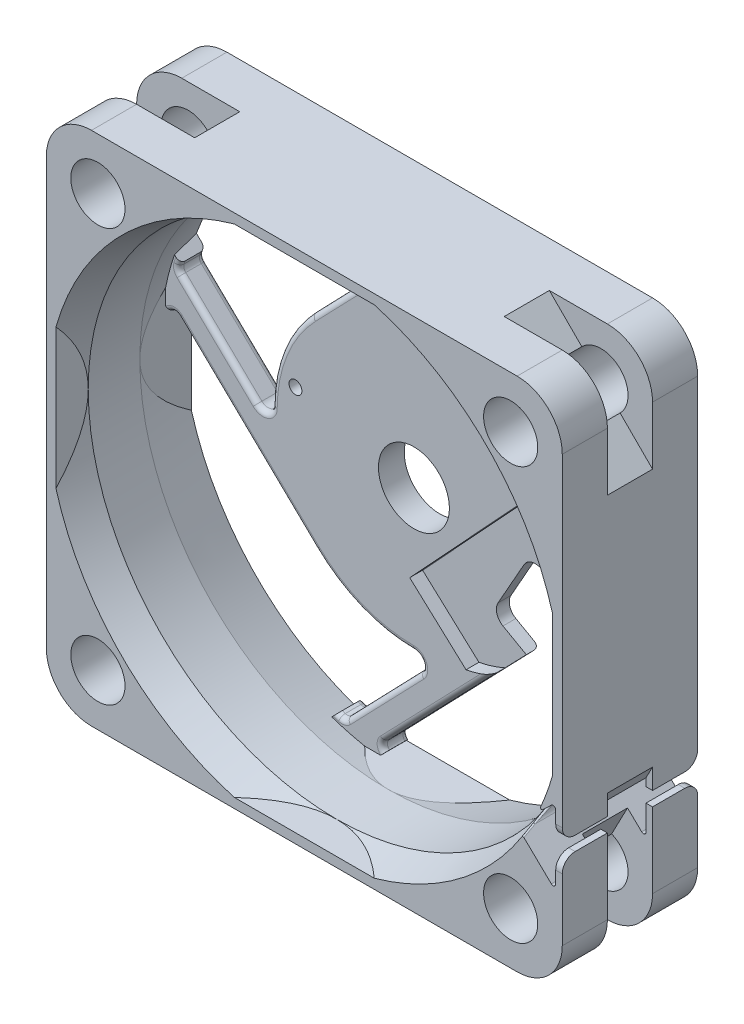
SolidWorks part; units mm, degrees
material "ПК/АБС"
ref_plane "Front" through (0, 0, 0) normal (0, 0, 1) x (1, 0, 0)
ref_plane "Top" through (0, 0, 0) normal (0, 1, 0) x (1, 0, 0)
ref_plane "Right" through (0, 0, 0) normal (1, 0, 0) x (0, 0, -1)
sketch "Эскиз1" plane through (0, 0, 0) normal (0, 0, 1) x (1, 0, 0)
  line L1 (-16.5, 20) -> (16.5, 20)
  line L2 (-20, 16.5) -> (-20, -16.5)
  line L3 (-16.5, -20) -> (16.5, -20)
  line L4 (20, 16.5) -> (20, -16.5)
  line L5 (0, -20) -> (0, 20) construction
  line L6 (-20, 0) -> (20, 0) construction
  arc A0 (16.5, 20) -> (20, 16.5) centre (16.5, 16.5) cw
  arc A1 (-20, -16.5) -> (-16.5, -20) centre (-16.5, -16.5) ccw
  arc A2 (-16.5, 20) -> (-20, 16.5) centre (-16.5, 16.5) ccw
  arc A3 (16.5, -20) -> (20, -16.5) centre (16.5, -16.5) ccw
  point P0 (0, 0)
  point P11 (-20, -20)
  point P14 (-20, 20)
  dimension "D2" = 3.5
  dimension "D1" = 40
extrude "Бобышка-Вытянуть1" add sketch "Эскиз1" along normal blind 10.5
sketch "Эскиз2" plane through (0, 0, 10.5) normal (0, 0, 1) x (1, 0, 0)
  circle A0 centre (0, 0) radius 19.25
  dimension "D1" = 38.5
extrude "Вырез-Вытянуть1" cut sketch "Эскиз2" against normal blind 10.5
sketch "Эскиз3" plane through (0, 0, 0) normal (0, 1, 0) x (1, 0, 0)
  line L0 (0, 0) -> (0, -4) construction
  line L1 (-16.5, 0) -> (16.5, 0) construction
  line L2 (0, -10.5) -> (0, -8) construction
  line L3 (-16.5, -10.5) -> (16.5, -10.5) construction
  line L4 (0, -10.5) -> (-20, -10.5)
  line L5 (-20, -10.5) -> (-19.25, -8)
  line L6 (-19.25, -8) -> (0, -8)
  line L7 (0, 0) -> (-20, 0)
  line L8 (-20, 0) -> (-19.25, -4)
  line L9 (-19.25, -4) -> (0, -4)
  line L10 (0, -10.5) -> (0, -8)
  line L11 (0, -4) -> (0, 0)
  dimension "D1" = 19.25
  dimension "D2" = 20
  dimension "D3" = 4
  dimension "D4" = 2.5
revolve "Вырез-Повернуть1" cut sketch "Эскиз3" angle 360 about L10
sketch "Эскиз4" plane through (0, 0, 10.5) normal (0, 0, 1) x (1, 0, 0)
  line L1 (16.5, -20) -> (-16.5, -20)
  line L2 (20, -16.5) -> (20, 16.5)
  line L3 (16.5, 20) -> (-16.5, 20)
  line L4 (-20, -16.5) -> (-20, 16.5)
  line L5 (0, 20) -> (0, -20) construction
  line L6 (20, 0) -> (-20, 0) construction
  line L7 (-15.75, 19.25) -> (15.75, 19.25)
  line L8 (-19.25, 15.75) -> (-19.25, -15.75)
  line L9 (-15.75, -19.25) -> (15.75, -19.25)
  line L10 (19.25, 15.75) -> (19.25, -15.75)
  line L11 (0, -19.25) -> (0, 19.25) construction
  line L12 (-19.25, 0) -> (19.25, 0) construction
  arc A0 (-16.5, -20) -> (-20, -16.5) centre (-16.5, -16.5) cw
  arc A1 (-19.25, -15.75) -> (-15.75, -19.25) centre (-15.75, -15.75) ccw
  arc A2 (15.75, -19.25) -> (19.25, -15.75) centre (15.75, -15.75) ccw
  arc A3 (16.5, -20) -> (20, -16.5) centre (16.5, -16.5) ccw
  arc A4 (15.75, 19.25) -> (19.25, 15.75) centre (15.75, 15.75) cw
  arc A5 (20, 16.5) -> (16.5, 20) centre (16.5, 16.5) ccw
  arc A6 (-16.5, 20) -> (-20, 16.5) centre (-16.5, 16.5) ccw
  arc A7 (-15.75, 19.25) -> (-19.25, 15.75) centre (-15.75, 15.75) ccw
  point P0 (0, 0)
  point P4 (0, 0)
  point P18 (-19.25, -19.25)
  point P23 (20, -20)
  point P28 (20, 20)
  point P33 (-19.25, 19.25)
  dimension "D3" = 3.5
  dimension "D1" = 40
  dimension "D2" = 38.5
extrude "Бобышка-Вытянуть2" add sketch "Эскиз4" against normal blind 10.5
sketch "Эскиз5" plane through (0, 0, 10.5) normal (0, 0, 1) x (1, 0, 0)
  line L1 (-16, 16) -> (16, 16) construction
  line L2 (-16, 16) -> (-16, -16) construction
  line L3 (-16, -16) -> (16, -16) construction
  line L4 (16, 16) -> (16, -16) construction
  line L5 (0, -16) -> (0, 16) construction
  line L6 (-16, 0) -> (16, 0) construction
  circle A0 centre (-16, 16) radius 2.1
  circle A1 centre (16, 16) radius 2.1
  circle A2 centre (16, -16) radius 2.1
  circle A3 centre (-16, -16) radius 2.1
  point P0 (0, 0)
  point P17 (0, 0)
  dimension "D2" = 4.2
  dimension "D1" = 32
  dimension "D3" = 4
extrude "Вырез-Вытянуть2" cut sketch "Эскиз5" against normal blind 10.5
sketch "Эскиз6" plane through (0, 0, 10.5) normal (0, 0, 1) x (1, 0, 0)
  line L0 (-12, 20) -> (-20, 12)
  line L1 (16.5, 20) -> (-16.5, 20) construction
  line L2 (-20, 16.5) -> (-20, -16.5) construction
  line L3 (0, 20) -> (0, -20) construction
  line L4 (-16.5, -20) -> (16.5, -20) construction
  line L5 (0, -20) -> (-20, 0) construction
  line L6 (-20, 0) -> (20, 0) construction
  line L7 (20, -16.5) -> (20, 16.5) construction
  line L8 (-12, 20) -> (-20, 20)
  line L9 (-20, 20) -> (-20, 12)
  line L10 (20, 20) -> (12, 20)
  line L11 (20, 12) -> (12, 20)
  line L12 (20, 12) -> (20, 20)
  line L13 (20, -20) -> (20, -12) construction
  line L14 (12, -20) -> (20, -12) construction
  line L15 (12, -20) -> (20, -20) construction
  line L16 (-20, -20) -> (-12, -20)
  line L17 (-20, -12) -> (-12, -20)
  line L18 (-20, -12) -> (-20, -20)
  line L19 (12, -20) -> (20, -8) construction
  line L20 (20, -8) -> (20, -20)
  line L21 (20, -20) -> (12, -20)
  line L22 (12, -20) -> (15.6268, -16.3732)
  line L23 (15.6268, -16.3732) -> (20, -8)
  point P27 (0, 0)
  dimension "D1" = 12
  dimension "D2" = 12
  dimension "D3" = 4
  dimension "D4" = 12
extrude "Вырез-Вытянуть3" cut sketch "Эскиз6" against normal blind 3.5 from offset 3.5 offset against normal yes
sketch "Эскиз7" plane through (0, 0, 0) normal (0, 0, -1) x (-1, 0, 0)
  line L0 (7.9198, 7.634) -> (-4, 20) construction
  line L1 (-20, 20) -> (20, 20) construction
  line L2 (-20, 20) -> (-20, -20) construction
  line L3 (-20, -20) -> (20, -20) construction
  line L4 (20, 20) -> (20, -20) construction
  line L5 (0, -20) -> (0, 20) construction
  line L6 (-20, 0) -> (20, 0) construction
  line L7 (-7.0556, 20) -> (1.7554, 10.859) construction
  line L8 (-3.3055, 20) -> (-2.299, 18.9558)
  line L9 (-7.7501, 20) -> (-5.9584, 18.1412)
  line L10 (-3.3055, 20) -> (-7.7501, 20)
  line L11 (-5.9584, 18.1412) -> (-6.6524, 18.8612) construction
  line L12 (-5.4246, 18.3079) -> (0.4766, 12.1858)
  line L13 (7.9198, 7.634) -> (-2.9121, 18.8713)
  line L14 (-2.299, 18.9558) -> (-2.9121, 18.8713)
  line L15 (-5.4246, 18.3079) -> (-5.9584, 18.1412)
  line L16 (20, 3.3055) -> (18.9558, 2.299)
  line L17 (20, 7.7501) -> (18.1412, 5.9584)
  line L18 (20, 3.3055) -> (20, 7.7501)
  line L19 (18.3079, 5.4246) -> (12.1858, -0.4766)
  line L20 (7.634, -7.9198) -> (18.8713, 2.9121)
  line L21 (18.9558, 2.299) -> (18.8713, 2.9121)
  line L22 (18.3079, 5.4246) -> (18.1412, 5.9584)
  line L23 (7.634, -7.9198) -> (20, 4) construction
  line L24 (20, 7.0556) -> (10.859, -1.7554) construction
  line L25 (18.1412, 5.9584) -> (18.8612, 6.6524) construction
  line L26 (3.3055, -20) -> (2.299, -18.9558)
  line L27 (7.7501, -20) -> (5.9584, -18.1412)
  line L28 (3.3055, -20) -> (7.7501, -20)
  line L29 (5.4246, -18.3079) -> (-0.4766, -12.1858)
  line L30 (-7.9198, -7.634) -> (2.9121, -18.8713)
  line L31 (2.299, -18.9558) -> (2.9121, -18.8713)
  line L32 (5.4246, -18.3079) -> (5.9584, -18.1412)
  line L33 (-7.9198, -7.634) -> (4, -20) construction
  line L34 (7.0556, -20) -> (-1.7554, -10.859) construction
  line L35 (5.9584, -18.1412) -> (6.6524, -18.8612) construction
  line L36 (-20, -3.3055) -> (-18.9558, -2.299)
  line L37 (-20, -7.7501) -> (-18.1412, -5.9584)
  line L38 (-20, -3.3055) -> (-20, -7.7501)
  line L39 (-18.3079, -5.4246) -> (-12.1858, 0.4766)
  line L40 (-7.634, 7.9198) -> (-18.8713, -2.9121)
  line L41 (-18.9558, -2.299) -> (-18.8713, -2.9121)
  line L42 (-18.3079, -5.4246) -> (-18.1412, -5.9584)
  line L43 (-7.634, 7.9198) -> (-20, -4) construction
  line L44 (-20, -7.0556) -> (-10.859, 1.7554) construction
  line L45 (-18.1412, -5.9584) -> (-18.8612, -6.6524) construction
  circle A0 centre (0, 0) radius 11 construction
  arc A1 (-5.4256, 19.25) -> (-19.25, 5.4256) centre (0, 0) ccw construction
  circle A2 centre (0, 0) radius 19.0947 construction
  arc A3 (-7.634, 7.9198) -> (-0.0258, 11) centre (0, 0) cw
  arc A4 (7.9198, 7.634) -> (11, 0.0258) centre (0, 0) cw
  arc A5 (7.634, -7.9198) -> (0.0258, -11) centre (0, 0) cw
  arc A6 (-7.9198, -7.634) -> (-11, -0.0258) centre (0, 0) cw
  arc A7 (-0.4766, -12.1858) -> (0.0258, -11) centre (0.0274, -11.7) cw
  arc A8 (-0.0258, 11) -> (0.4766, 12.1858) centre (-0.0274, 11.7) ccw
  arc A9 (12.1858, -0.4766) -> (11, 0.0258) centre (11.7, 0.0274) cw
  arc A10 (-12.1858, 0.4766) -> (-11, -0.0258) centre (-11.7, -0.0274) cw
  point P62 (0, 0)
  dimension "D1" = 22
  dimension "D8" = 4
  dimension "D10" = 0.7
  dimension "D2" = 40
  dimension "D3" = 16
  dimension "D4" = 2.2
  dimension "D5" = 0.5
  dimension "D6" = 0.5
  dimension "D7" = 1
extrude "Бобышка-Вытянуть3" add sketch "Эскиз7" against normal blind 2
fillet "Скругление4" radius 0.5 8 edges at (2.9121, 18.8713, 1) (5.4246, 18.3079, 1) (18.8713, -2.9121, 1) (18.3079, -5.4246, 1) (-18.8713, 2.9121, 1) (-18.3079, 5.4246, 1) (-5.4246, -18.3079, 1) (-2.9121, -18.8713, 1)
fillet "Скругление1" radius 0.4 56 edges at (10.1961, -4.1279, 2) (-12.9414, -2.8039, 2) (-2.8039, 12.9414, 2) (4.1279, 10.1961, 2) (10.1961, -4.1279, 0) (-4.1279, -10.1961, 0) (-2.8039, 12.9414, 0) (4.1279, 10.1961, 0) (-2.3669, -15.1357, 0) (-15.1357, 2.3669, 0) (2.8039, -12.9414, 2) (-4.1279, -10.1961, 2) (-2.3669, -15.1357, 2) (-10.1961, 4.1279, 2) (-15.1357, 2.3669, 2) (12.9414, 2.8039, 2) (15.1357, -2.3669, 2) (2.8039, -12.9414, 0) (-12.9414, -2.8039, 0) (-10.1961, 4.1279, 0) (12.9414, 2.8039, 0) (15.1357, -2.3669, 0) (2.3669, 15.1357, 2) (2.3669, 15.1357, 0) (0.6171, -11.4269, 2) (-11.4269, -0.6171, 2) (11.4269, 0.6171, 2) (0.6171, -11.4269, 0) (-11.4269, -0.6171, 0) (11.4269, 0.6171, 0) (-0.6171, 11.4269, 2) (-0.6171, 11.4269, 0) (-5.8389, -18.1786, 2) (-5.4464, -18.223, 2) (-18.605, 2.4519, 2) (-18.1786, 5.8389, 2) (-18.223, 5.4464, 2) (2.4519, 18.605, 2) (18.1786, -5.8389, 2) (18.223, -5.4464, 2) (-2.4519, -18.605, 2) (-5.8389, -18.1786, 0) (-5.4464, -18.223, 0) (-18.605, 2.4519, 0) (-18.1786, 5.8389, 0) (-18.223, 5.4464, 0) (2.4519, 18.605, 0) (18.1786, -5.8389, 0) (18.223, -5.4464, 0) (-2.4519, -18.605, 0) (5.8389, 18.1786, 2) (5.4464, 18.223, 2) (18.605, -2.4519, 2) (5.8389, 18.1786, 0) (5.4464, 18.223, 0) (18.605, -2.4519, 0)
sketch "Эскиз8" plane through (0, 0, 0) normal (0, 0, -1) x (-1, 0, 0)
  line L0 (-2.4337, 19.0955) -> (-3.1935, 19.8837)
  line L1 (-3.1935, 19.8837) -> (-7.1798, 19.4084)
  line L2 (-7.1798, 19.4084) -> (-6.078, 18.2653)
  line L3 (-6.6524, 18.8612) -> (-6.2689, 18.4633) construction
  line L7 (-2.5766, 19.2438) -> (-2.5826, 19.25) construction
  line L8 (19.0955, 2.4337) -> (19.8837, 3.1935)
  line L9 (19.8837, 3.1935) -> (19.4084, 7.1798)
  line L10 (19.4084, 7.1798) -> (18.2653, 6.078)
  line L11 (2.4337, -19.0955) -> (3.1935, -19.8837)
  line L12 (3.1935, -19.8837) -> (7.1798, -19.4084)
  line L13 (7.1798, -19.4084) -> (6.078, -18.2653)
  line L14 (-19.0955, -2.4337) -> (-19.8837, -3.1935)
  line L15 (-19.8837, -3.1935) -> (-19.4084, -7.1798)
  line L16 (-19.4084, -7.1798) -> (-18.2653, -6.078)
  circle A0 centre (0, 0) radius 19.25 construction
  circle A1 centre (0, 0) radius 19.25 construction
  arc A2 (-6.078, 18.2653) -> (-2.4337, 19.0955) centre (0, 0) cw
  arc A3 (18.2653, 6.078) -> (19.0955, 2.4337) centre (0, 0) cw
  arc A4 (6.078, -18.2653) -> (2.4337, -19.0955) centre (0, 0) cw
  arc A5 (-18.2653, -6.078) -> (-19.0955, -2.4337) centre (0, 0) cw
  point P29 (0, 0)
  dimension "D2" = 4
extrude "Бобышка-Вытянуть4" add sketch "Эскиз8" against normal blind 4 contours A2 L0 L1 L2
sketch "Эскиз9" plane through (0, 0, 0) normal (0, 0, -1) x (-1, 0, 0)
  line L1 (-19.1541, -12.7668) -> (-16.7846, -10.4828)
  line L2 (-18.3632, -4.9224) -> (-12.4634, 0.7646) construction
  line L3 (-16.7846, -9.7628) -> (-19.1541, -7.4788)
  line L4 (-19.4929, -7.6228) -> (-19.4929, -12.6228) construction
  line L5 (-19.4929, -9.5728) -> (-23.1933, -9.5728)
  line L6 (-23.1933, -9.5728) -> (-23.1933, -10.6728)
  line L7 (-23.1933, -10.6728) -> (-19.4929, -10.6728)
  line L8 (-19.4929, -10.6728) -> (-19.4929, -12.6228)
  line L9 (-19.4929, -9.5728) -> (-19.4929, -7.6228)
  line L10 (-19.4929, -10.1228) -> (-23.1933, -10.1228) construction
  arc A0 (-16.7846, -10.4828) -> (-16.7846, -9.7628) centre (-17.1316, -10.1228) ccw
  arc A1 (-19.1541, -12.7668) -> (-19.4929, -12.6228) centre (-19.2929, -12.6228) cw
  arc A2 (-19.1541, -7.4788) -> (-19.4929, -7.6228) centre (-19.2929, -7.6228) ccw
  point P12 (-19.4929, -13.0934)
  point P15 (-19.4929, -7.1522)
  point P23 (-23.1933, -10.1228)
  dimension "D2" = 0.5
  dimension "D3" = 0.2
  dimension "D4" = 5
  dimension "D5" = 1.1
extrude "Вырез-Вытянуть4" cut sketch "Эскиз9" against normal through all
fillet "Скругление2" radius 1 4 edges at (19.7465, -10.6728, 0) (19.7465, -9.5728, 0) (19.7465, -10.6728, 10.5) (19.7465, -9.5728, 10.5)
sketch "Эскиз10" plane through (0, 0, 0) normal (0, 0, -1) x (-1, 0, 0)
  circle A0 centre (0, 0) radius 2.75
  dimension "D1" = 5.5
extrude "Вырез-Вытянуть5" cut sketch "Эскиз10" against normal through all
sketch "Эскиз11" plane through (0, 0, 0) normal (0, 0, -1) x (-1, 0, 0)
  line L0 (-12.2669, -3.4171) -> (-8.8958, -1.5167)
  line L1 (-7.5336, -1.8967) -> (-5.523, -5.4635)
  line L2 (-5.903, -6.8257) -> (-9.2742, -8.726)
  line L3 (-9.2742, -8.726) -> (-12.2669, -3.4171)
  line L4 (0, 0) -> (-23.3748, -13.1768) construction
  arc A0 (-5.523, -5.4635) -> (-5.903, -6.8257) centre (-6.3941, -5.9545) cw
  arc A1 (-8.8958, -1.5167) -> (-7.5336, -1.8967) centre (-8.4047, -2.3878) cw
  point P12 (-6.5283, -3.6801)
  dimension "D1" = 1
extrude "Вырез-Вытянуть6" cut sketch "Эскиз11" against normal blind 10
sketch "Эскиз12" plane through (0, 0, 0) normal (0, 0, -1) x (-1, 0, 0)
  circle A0 centre (9.1859, 2.1589) radius 0.5
  dimension "D1" = 1
extrude "Вырез-Вытянуть7" cut sketch "Эскиз12" against normal blind 10
fillet "Скругление5" radius 0.1 6 edges at (16.6685, -9.9343, 8.5144) (16.6813, -9.9055, 3.1968)
sketch "Эскиз13" plane through (0, 0, 0) normal (0, 0, -1) x (-1, 0, 0)
  line L0 (-11, -0.0258) -> (-8.094, 2.8802)
  line L1 (-8.094, 2.8802) -> (0.3276, -6.1966)
  line L2 (0.3276, -6.1966) -> (-4.04, -10.1961)
  arc A0 (-11, -0.0258) -> (-4.04, -10.1961) centre (-2.4348, -1.631) ccw
extrude "Вырез-Вытянуть8" cut sketch "Эскиз13" against normal blind 10 from offset 1 offset against normal yes
